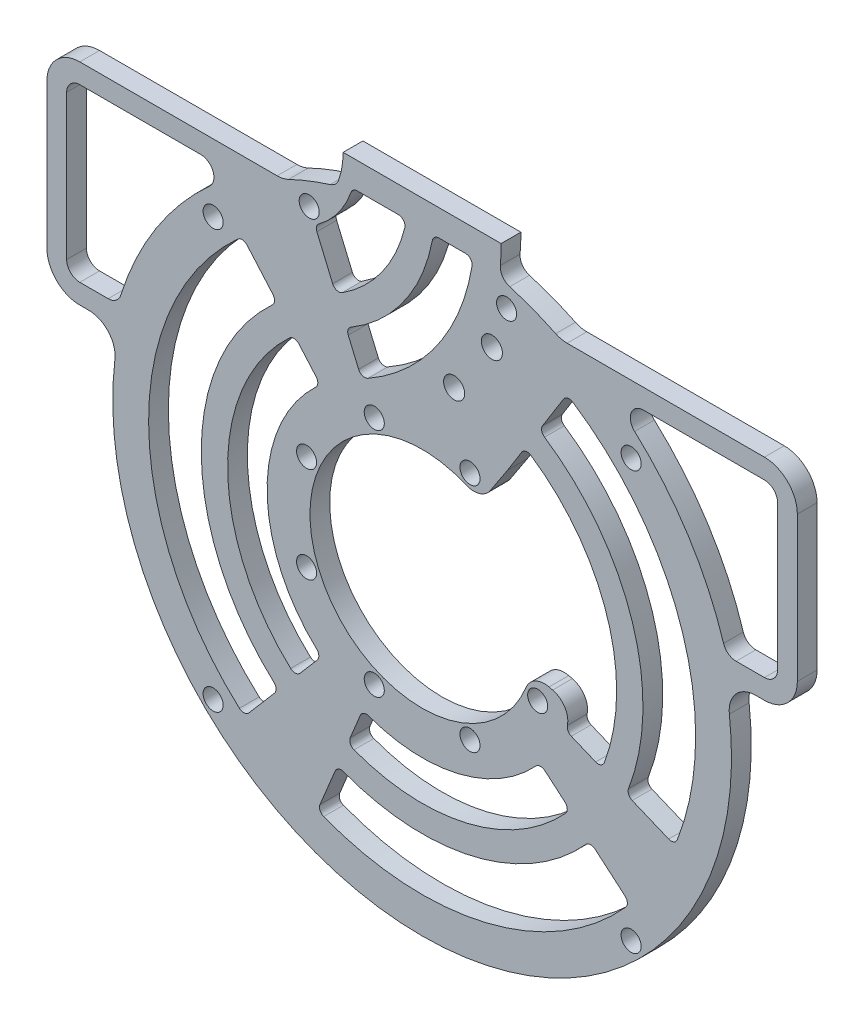
SolidWorks part; units mm, degrees
material "Thornel Mat VMA"
ref_plane "前视基准面" through (0, 0, 0) normal (0, 0, 1) x (1, 0, 0)
ref_plane "上视基准面" through (0, 0, 0) normal (0, 1, 0) x (1, 0, 0)
ref_plane "右视基准面" through (0, 0, 0) normal (1, 0, 0) x (0, 0, -1)
sketch "草图1" plane through (0, 0, 0) normal (0, 0, 1) x (1, 0, 0)
  line L0 (0, 0) -> (0, 50.1) construction
  line L1 (0, 50.1) -> (0, 73.1) construction
  line L2 (-35.5, 73.1) -> (35.5, 73.1) construction
  line L3 (-12, 50.1) -> (12, 50.1)
  line L4 (0, 0) -> (12.8351, 41.9818) construction
  line L5 (0, 0) -> (-17.1531, 40.4102) construction
  circle A0 centre (0, 0) radius 17.04
  circle A1 centre (0, 0) radius 40.9 construction
  circle A2 centre (0, 0) radius 19 construction
  circle A3 centre (-7.271, 17.5537) radius 1.525
  circle A4 centre (7.271, 17.5537) radius 1.525
  circle A5 centre (17.5537, 7.271) radius 1.525
  circle A6 centre (17.5537, -7.271) radius 1.525
  circle A7 centre (0, 0) radius 46.4 construction
  circle A8 centre (-35.5, 73.1) radius 30 construction
  circle A9 centre (35.5, 73.1) radius 30 construction
  arc A10 (0, 50.1) -> (-6.8598, 33.3008) centre (-24, 50.1) cw construction
  circle A11 centre (0, 0) radius 34 construction
  circle A12 centre (-1.2412, 42.4819) radius 8.5 construction
  circle A13 centre (0, 59.4365) radius 8.5 construction
  arc A15 (-13.9709, 44.8755) -> (13.3067, 45.077) centre (0, 0) ccw
  arc A18 (-12, 50.1) -> (-12.6785, 46.1222) centre (-24, 50.1) cw
  arc A19 (12, 50.1) -> (11.8796, 47.1585) centre (-24, 50.1) cw
  arc A20 (-12.6785, 46.1222) -> (-13.9709, 44.8755) centre (-14.5654, 46.7851) cw
  arc A21 (11.8796, 47.1585) -> (13.3067, 45.077) centre (13.8729, 46.9951) ccw
  circle A22 centre (-17.1531, 40.4102) radius 1.525
  circle A23 centre (12.8351, 41.9818) radius 1.525
  circle A24 centre (7.271, -17.5537) radius 1.525
  circle A25 centre (-7.271, -17.5537) radius 1.525
  circle A26 centre (-17.5537, -7.271) radius 1.525
  circle A27 centre (-17.5537, 7.271) radius 1.525
  point P17 (0, 0)
  dimension "D2" = 34.08
  dimension "D3" = 81.8
  dimension "D4" = 38
  dimension "D6" = 3.05
  dimension "D8" = 60
  dimension "D10" = 24
  dimension "D11" = 68
  dimension "D12" = 17
  dimension "D13" = 92.8
  dimension "D14" = 94
  dimension "D16" = 2
  dimension "D17" = 3.05
  dimension "D1" = 50.1
  dimension "D7" = 71
  dimension "D9" = 23
  dimension "D15" = 24
  dimension "D18" = 43.9
  dimension "D19" = 17
  dimension "D20" = 40
  dimension "D5" = 8
extrude "凸台-拉伸1" add sketch "草图1" along normal blind 3
sketch "草图2" plane through (0, 0, 3) normal (0, 0, 1) x (1, 0, 0)
  circle A0 centre (0, 0) radius 44.9 construction
  circle A1 centre (-31.7491, 31.7491) radius 1.525
  circle A2 centre (31.7491, 31.7491) radius 1.525
  circle A3 centre (31.7491, -31.7491) radius 1.525
  circle A4 centre (-31.7491, -31.7491) radius 1.525
  point P15 (0, 0)
  dimension "D2" = 3.05
  dimension "D3" = 89.8
  dimension "D1" = 4
extrude "切除-拉伸1" cut sketch "草图2" against normal blind 10
sketch "草图3" plane through (0, 0, 3) normal (0, 0, 1) x (1, 0, 0)
  line L0 (0, 0) -> (0, 17.04) construction
  line L1 (0, 0) -> (4.8621, 27.5746) construction
  line L2 (4.8621, 27.5746) -> (10.5979, 35.7661) construction
  circle A0 centre (0, 0) radius 17.04 construction
  circle A1 centre (4.8621, 27.5746) radius 1.6
  circle A2 centre (10.5979, 35.7661) radius 1.6
  dimension "D5" = 3.2
  dimension "D1" = 28
  dimension "D2" = 10
  dimension "D3" = 10
  dimension "D4" = 25
extrude "切除-拉伸2" cut sketch "草图3" against normal blind 8
sketch "草图4" plane through (0, 0, 3) normal (0, 0, 1) x (1, 0, 0)
  line L0 (-52, 42) -> (-21.095, 42)
  line L1 (-57, 37) -> (-57, 15)
  line L2 (-52, 10) -> (-45.9239, 10)
  line L3 (0, 0) -> (0, 50.1) construction
  line L4 (12, 50.1) -> (-12, 50.1) construction
  line L5 (-33.6303, 39) -> (-52, 39)
  line L6 (-54, 37) -> (-54, 15)
  line L7 (-52, 13) -> (-47.697, 13)
  line L8 (52, 13) -> (47.697, 13)
  line L9 (54, 37) -> (54, 15)
  line L10 (33.6303, 39) -> (52, 39)
  line L11 (57, 37) -> (57, 15)
  line L12 (52, 10) -> (45.9239, 10)
  line L13 (52, 42) -> (21.095, 42)
  arc A0 (-13.9709, 44.8755) -> (13.3067, 45.077) centre (0, 0) ccw construction
  arc A1 (-45.9239, 10) -> (-21.095, 42) centre (0, 0) cw
  arc A2 (-45.7891, 14.4) -> (-32.2851, 35.52) centre (0, 0) cw
  arc A3 (-54, 15) -> (-52, 13) centre (-52, 15) ccw
  arc A4 (-52, 39) -> (-54, 37) centre (-52, 37) ccw
  arc A5 (-32.2851, 35.52) -> (-33.6303, 39) centre (-33.6303, 37) ccw
  arc A6 (-47.697, 13) -> (-45.7891, 14.4) centre (-47.697, 15) ccw
  arc A7 (-57, 15) -> (-52, 10) centre (-52, 15) ccw
  arc A8 (-52, 42) -> (-57, 37) centre (-52, 37) ccw
  arc A9 (45.7891, 14.4) -> (32.2851, 35.52) centre (0, 0) ccw
  arc A10 (47.697, 13) -> (45.7891, 14.4) centre (47.697, 15) cw
  arc A11 (54, 15) -> (52, 13) centre (52, 15) cw
  arc A12 (52, 39) -> (54, 37) centre (52, 37) cw
  arc A13 (32.2851, 35.52) -> (33.6303, 39) centre (33.6303, 37) cw
  arc A14 (57, 15) -> (52, 10) centre (52, 15) cw
  arc A15 (45.9239, 10) -> (21.095, 42) centre (0, 0) ccw
  arc A16 (52, 42) -> (57, 37) centre (52, 37) cw
  dimension "D4" = 1
  dimension "D8" = 2
  dimension "D9" = 2
  dimension "D10" = 5
  dimension "D1" = 114
  dimension "D2" = 10
  dimension "D3" = 42
  dimension "D5" = 3
  dimension "D6" = 3
  dimension "D7" = 3
extrude "凸台-拉伸2" add sketch "草图4" against normal up to surface (3 mm away) up to face at (3.2621, 27.5746, 0)
fillet "圆角1" radius 4 4 edges at (45.9239, 10, 1.5) (21.095, 42, 1.5) (-21.095, 42, 1.5) (-45.9239, 10, 1.5)
sketch "草图5" plane through (0, 0, 3) normal (0, 0, 1) x (1, 0, 0)
  line L0 (-1.0217, 50.1) -> (-24, 50.1) construction
  line L1 (-24, 50.1) -> (0, 0) construction
  line L2 (-24, 50.1) -> (-10.5836, 46.1) construction
  line L3 (0, 0) -> (12.8351, 41.9818) construction
  line L4 (-9.8579, 46.1) -> (-3.6039, 46.1)
  line L5 (-12, 50.1) -> (12, 50.1) construction
  line L6 (2.533, 46.1) -> (6.5941, 46.1)
  line L7 (0, 0) -> (22.0191, 35.238) construction
  line L8 (15.1209, 24.1985) -> (12.9997, 20.8039)
  line L9 (18.302, 29.2894) -> (21.4827, 34.3795)
  line L10 (0, 0) -> (38.3889, -15.9012) construction
  line L11 (0, 0) -> (31.5963, -26.9858) construction
  line L12 (0, 0) -> (-26.9858, -31.5963) construction
  line L13 (0, 0) -> (-15.9012, -38.3889) construction
  line L14 (0, 0) -> (-16.3024, 38.4061) construction
  line L15 (0, 0) -> (-17.1531, 40.4102) construction
  line L16 (0, 0) -> (-27.2605, 31.3596) construction
  line L17 (-15.9859, 37.6605) -> (-13.5941, 32.0256)
  line L18 (-11.2237, 26.4413) -> (-9.6491, 22.7318)
  line L19 (-16.0941, 18.5142) -> (-18.7202, 21.5351)
  line L20 (-22.6586, 26.0657) -> (-26.5963, 30.5956)
  line L21 (-18.5316, -21.6977) -> (-15.9319, -18.6539)
  line L22 (-22.4302, -26.2624) -> (-26.3283, -30.8265)
  line L23 (-10.9196, -26.3623) -> (-9.3878, -22.6641)
  line L24 (-13.2169, -31.9084) -> (-15.5138, -37.4536)
  line L25 (30.8265, -26.3283) -> (26.2624, -22.4302)
  line L26 (21.6977, -18.5316) -> (18.6539, -15.9319)
  line L27 (22.6641, -9.3878) -> (26.3623, -10.9196)
  line L28 (31.9084, -13.2169) -> (37.4536, -15.5138)
  arc A0 (-13.6313, 28.4554) -> (-0.0227, 49.0565) centre (-24, 50.1) ccw construction
  arc A1 (-13.6313, 28.4554) -> (9.2249, 30.1732) centre (0, 0) ccw construction
  arc A2 (-20.157, 21.6104) -> (-19.9677, -21.7854) centre (0, 0) ccw
  arc A3 (-10.8105, 27.6938) -> (1.5503, 45.2852) centre (-24, 50.1) ccw
  arc A4 (-22.7357, 24.6742) -> (-22.5195, -24.8717) centre (0, 0) ccw
  arc A5 (-12.1342, 31.5743) -> (-2.6327, 44.8619) centre (-24, 50.1) ccw
  arc A6 (-16.1626, 17.1307) -> (-16.0125, -17.2711) centre (0, 0) ccw
  arc A7 (-8.2359, 22.2523) -> (7.581, 44.9387) centre (-24, 50.1) ccw
  arc A8 (-28.0255, 30.6778) -> (-27.7567, -30.9212) centre (0, 0) ccw
  arc A9 (-15.6611, 38.8545) -> (-10.8007, 45.4333) centre (-24, 50.1) ccw
  arc A10 (-17.9516, 37.474) -> (-10, 50.1) centre (-24, 50.1) ccw construction
  arc A11 (-14.4954, 30.2591) -> (-2, 50.1) centre (-24, 50.1) ccw construction
  arc A12 (-12.7673, 26.6516) -> (2, 50.1) centre (-24, 50.1) ccw construction
  arc A13 (-10.1751, 21.2405) -> (8, 50.1) centre (-24, 50.1) ccw construction
  arc A14 (-17.9516, 37.474) -> (12.1486, 39.7362) centre (0, 0) ccw construction
  arc A15 (-14.4954, 30.2591) -> (9.8096, 32.0858) centre (0, 0) ccw construction
  arc A16 (-12.7673, 26.6516) -> (8.6401, 28.2606) centre (0, 0) ccw construction
  arc A17 (-10.1751, 21.2405) -> (6.8859, 22.5228) centre (0, 0) ccw construction
  arc A18 (22.1081, -8.1192) -> (13.2837, 19.4482) centre (0, 0) ccw
  arc A19 (27.6817, -10.3458) -> (16.5282, 24.4976) centre (0, 0) ccw
  arc A20 (31.3565, -11.9372) -> (18.5958, 27.9271) centre (0, 0) ccw
  arc A21 (38.7694, -14.9497) -> (22.8814, 34.6843) centre (0, 0) ccw
  arc A22 (-10.3458, -27.6817) -> (21.7854, -19.9677) centre (0, 0) ccw
  arc A23 (-11.9372, -31.3565) -> (24.8717, -22.5195) centre (0, 0) ccw
  arc A24 (-8.1192, -22.1081) -> (17.2711, -16.0125) centre (0, 0) ccw
  arc A25 (-14.9497, -38.7694) -> (30.9212, -27.7567) centre (0, 0) ccw
  arc A26 (-8.1192, -22.1081) -> (-9.3878, -22.6641) centre (-8.4639, -23.0468) ccw
  arc A27 (-16.0125, -17.2711) -> (-15.9319, -18.6539) centre (-16.6923, -18.0044) cw
  arc A28 (-11.9372, -31.3565) -> (-13.2169, -31.9084) centre (-12.293, -32.2911) ccw
  arc A29 (-22.5195, -24.8717) -> (-22.4302, -26.2624) centre (-23.1906, -25.613) cw
  arc A30 (-10.3458, -27.6817) -> (-10.9196, -26.3623) centre (-9.9957, -26.745) cw
  arc A31 (-19.9677, -21.7854) -> (-18.5316, -21.6977) centre (-19.292, -21.0482) ccw
  arc A32 (31.3565, -11.9372) -> (31.9084, -13.2169) centre (32.2911, -12.293) ccw
  arc A33 (26.2624, -22.4302) -> (24.8717, -22.5195) centre (25.613, -23.1906) ccw
  arc A34 (27.6817, -10.3458) -> (26.3623, -10.9196) centre (26.745, -9.9957) cw
  arc A35 (21.6977, -18.5316) -> (21.7854, -19.9677) centre (21.0482, -19.292) cw
  arc A36 (22.1081, -8.1192) -> (22.6641, -9.3878) centre (23.0468, -8.4639) ccw
  arc A37 (18.6539, -15.9319) -> (17.2711, -16.0125) centre (18.0044, -16.6923) ccw
  arc A38 (-16.1626, 17.1307) -> (-16.0941, 18.5142) centre (-16.8488, 17.8581) ccw
  arc A39 (-8.2359, 22.2523) -> (-9.6491, 22.7318) centre (-8.7286, 23.1225) cw
  arc A40 (-20.157, 21.6104) -> (-18.7202, 21.5351) centre (-19.4749, 20.8791) cw
  arc A41 (-10.8105, 27.6938) -> (-11.2237, 26.4413) centre (-10.3032, 26.8321) ccw
  arc A42 (-12.1342, 31.5743) -> (-13.5941, 32.0256) centre (-12.6736, 32.4163) cw
  arc A43 (-22.7357, 24.6742) -> (-22.6586, 26.0657) centre (-23.4133, 25.4096) ccw
  arc A44 (-28.0255, 30.6778) -> (-26.5963, 30.5956) centre (-27.351, 29.9395) cw
  arc A45 (-15.6611, 38.8545) -> (-15.9859, 37.6605) centre (-15.0654, 38.0512) ccw
  arc A46 (-27.7567, -30.9212) -> (-26.3283, -30.8265) centre (-27.0887, -30.1771) ccw
  arc A47 (-14.9497, -38.7694) -> (-15.5138, -37.4536) centre (-14.5899, -37.8363) cw
  arc A48 (30.8265, -26.3283) -> (30.9212, -27.7567) centre (30.1771, -27.0887) cw
  arc A49 (38.7694, -14.9497) -> (37.4536, -15.5138) centre (37.8363, -14.5899) cw
  arc A50 (13.2837, 19.4482) -> (12.9997, 20.8039) centre (13.8478, 20.274) cw
  arc A51 (16.5282, 24.4976) -> (15.1209, 24.1985) centre (15.969, 23.6686) ccw
  arc A52 (22.8814, 34.6843) -> (21.4827, 34.3795) centre (22.3307, 33.8496) ccw
  arc A53 (18.5958, 27.9271) -> (18.302, 29.2894) centre (19.1501, 28.7595) cw
  arc A54 (1.5503, 45.2852) -> (2.533, 46.1) centre (2.533, 45.1) cw
  arc A55 (-2.6327, 44.8619) -> (-3.6039, 46.1) centre (-3.6039, 45.1) ccw
  arc A56 (6.5941, 46.1) -> (7.581, 44.9387) centre (6.5941, 45.1) cw
  arc A57 (-10.8007, 45.4333) -> (-9.8579, 46.1) centre (-9.8579, 45.1) cw
  arc A58 (-13.6313, 28.4554) -> (0, 50.1) centre (-24, 50.1) ccw construction
  arc A59 (-1.0217, 50.1) -> (-0.0227, 49.0565) centre (-1.0217, 49.1) cw construction
  point P71 (-9.0129, -21.7591)
  point P74 (-15.2957, -17.909)
  point P77 (-12.8397, -30.9979)
  point P80 (-21.7902, -25.513)
  point P83 (-11.309, -27.3024)
  point P86 (-19.1924, -22.4714)
  point P89 (30.9979, -12.8397)
  point P92 (25.513, -21.7902)
  point P95 (27.3024, -11.309)
  point P98 (22.4714, -19.1924)
  point P101 (21.7591, -9.0129)
  point P104 (17.909, -15.2957)
  point P107 (-15.4514, 17.7748)
  point P110 (-9.2189, 21.7183)
  point P113 (-19.3878, 22.3031)
  point P116 (-11.5722, 27.2625)
  point P119 (-13.1439, 30.9651)
  point P122 (-22.012, 25.3219)
  point P143 (12.4806, 19.9731)
  point P146 (15.6601, 25.0614)
  point P152 (17.7798, 28.4536)
  point P155 (1.6905, 46.1)
  point P166 (0, 50.1)
  dimension "D10" = 1
  dimension "D5" = 4
  dimension "D6" = 15
  dimension "D7" = 18
  dimension "D8" = 18
  dimension "D9" = 18
  dimension "D1" = 2
  dimension "D2" = 2
  dimension "D3" = 8
  dimension "D4" = 10
extrude "切除-拉伸3" cut sketch "草图5" against normal blind 10
sketch "草图6" plane through (0, 0, 3) normal (0, 0, 1) x (1, 0, 0)
  line L0 (8.8812, 14.5426) -> (12.9997, 20.8039)
  line L1 (15.1209, 24.1985) -> (12.9997, 20.8039) construction
  line L2 (16.575, -3.9534) -> (22.9092, -5.4642)
  line L3 (22.9092, -5.4642) -> (25.9092, -5.4642)
  line L4 (25.9092, -5.4642) -> (25.9092, 10.842)
  line L5 (25.9092, 10.842) -> (12.9997, 20.8039)
  line L6 (8.8812, 14.5426) -> (16.575, -3.9534)
  circle A0 centre (0, 0) radius 17.04 construction
  arc A1 (12.9997, 20.8039) -> (13.2837, 19.4482) centre (13.8478, 20.274) ccw construction
  circle A2 centre (7.271, 17.5537) radius 1.525 construction
  arc A3 (22.1081, -8.1192) -> (13.2837, 19.4482) centre (0, 0) ccw construction
  circle A4 centre (17.5537, -7.271) radius 1.525 construction
  dimension "D1" = 3
  dimension "D2" = 3
  dimension "D3" = 3
extrude "切除-拉伸4" cut sketch "草图6" against normal blind 10
fillet "圆角2" radius 3 3 edges at (16.575, -3.9534, 1.5) (22.9092, -5.4642, 1.5) (8.8812, 14.5426, 1.5)
